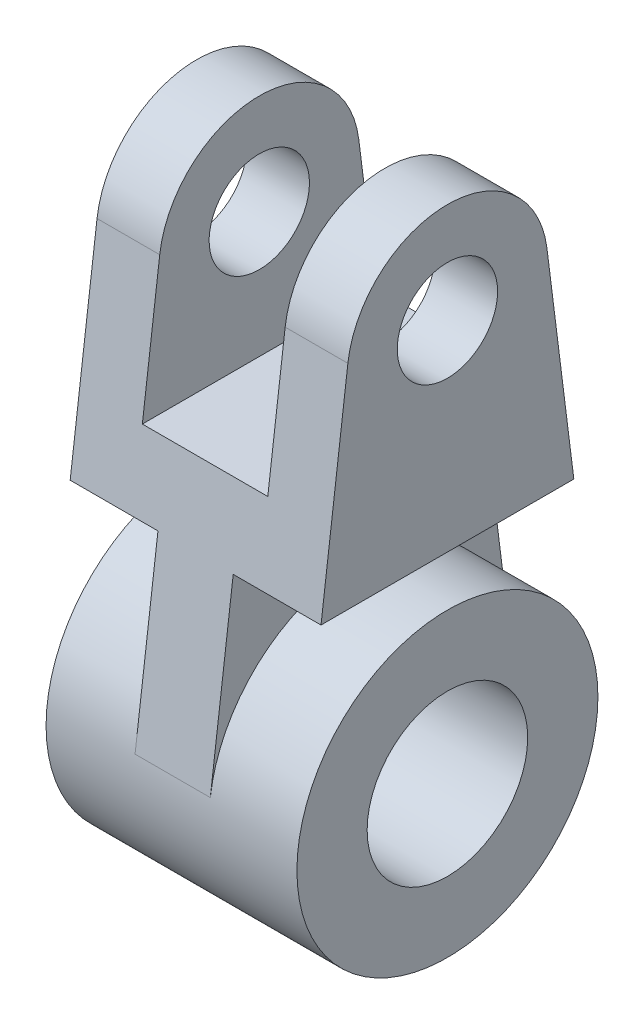
SolidWorks part; units mm, degrees
ref_plane "Front Plane" through (0, 0, 0) normal (0, 0, 1) x (1, 0, 0)
ref_plane "Top Plane" through (0, 0, 0) normal (0, 1, 0) x (1, 0, 0)
ref_plane "Right Plane" through (0, 0, 0) normal (1, 0, 0) x (0, 0, -1)
sketch "Sketch1" plane through (0, 0, 0) normal (1, 0, 0) x (0, 0, -1)
  circle A0 centre (0, 0) radius 30
  dimension "D1" = 60
extrude "Boss-Extrude1" add sketch "Sketch1" along normal mid plane 50
sketch "Sketch2" plane through (25, 0, 0) normal (1, 0, 0) x (0, 0, -1)
  circle A0 centre (0, 0) radius 16
  dimension "D1" = 32
extrude "Cut-Extrude1" cut sketch "Sketch2" against normal through all
sketch "Sketch3" plane through (0, 0, 0) normal (1, 0, 0) x (0, 0, -1)
  line L0 (0, 0) -> (0, 80) construction
  line L1 (-25.1976, 40) -> (25.1976, 40)
  line L2 (29.7647, 3.75) -> (19.8431, 82.5)
  line L3 (-19.8431, 82.5) -> (-29.7647, 3.75)
  arc A0 (19.8431, 82.5) -> (-19.8431, 82.5) centre (0, 80) ccw
  circle A1 centre (0, 0) radius 30 construction
  circle A2 centre (0, 0) radius 30
  point P4 (0, 100)
  dimension "D3" = 20
  dimension "D1" = 60
  dimension "D2" = 80
extrude "Boss-Extrude2" add sketch "Sketch3" along normal mid plane 50 separate body contours L2 A0 L3 L1 region at (0, 66.7796, 0)
extrude "Boss-Extrude3" add sketch "Sketch3<3>" along normal mid plane 15 contours A2 L0 L1 L3 | L0 A2 L2 L1 region at (0, 31.1344, 15.9348) region at (0, 31.1344, -15.9348)
sketch "Sketch3<3>" plane through (0, 0, 0) normal (1, 0, 0) x (0, 0, -1) same geometry as "Sketch3"
sketch "Sketch4" plane through (25, 0, 0) normal (1, 0, 0) x (0, 0, -1)
  circle A0 centre (0, 80) radius 10
  dimension "D1" = 20
extrude "Cut-Extrude2" cut sketch "Sketch4" against normal through all
sketch "Sketch5" plane through (0, 0, 0) normal (0, 0, 1) x (1, 0, 0)
  line L0 (25, 100) -> (-25, 100) construction
  line L1 (12.5, 100) -> (-12.5, 100)
  line L2 (12.5, 100) -> (12.5, 55)
  line L3 (12.5, 55) -> (-12.5, 55)
  line L4 (-12.5, 100) -> (-12.5, 55)
  line L5 (-25, 100) -> (-25, 82.5) construction
  dimension "D1" = 25
  dimension "D2" = 45
  dimension "D3" = 12.5
extrude "Cut-Extrude3" cut sketch "Sketch5" against normal through all both and the other way through all
